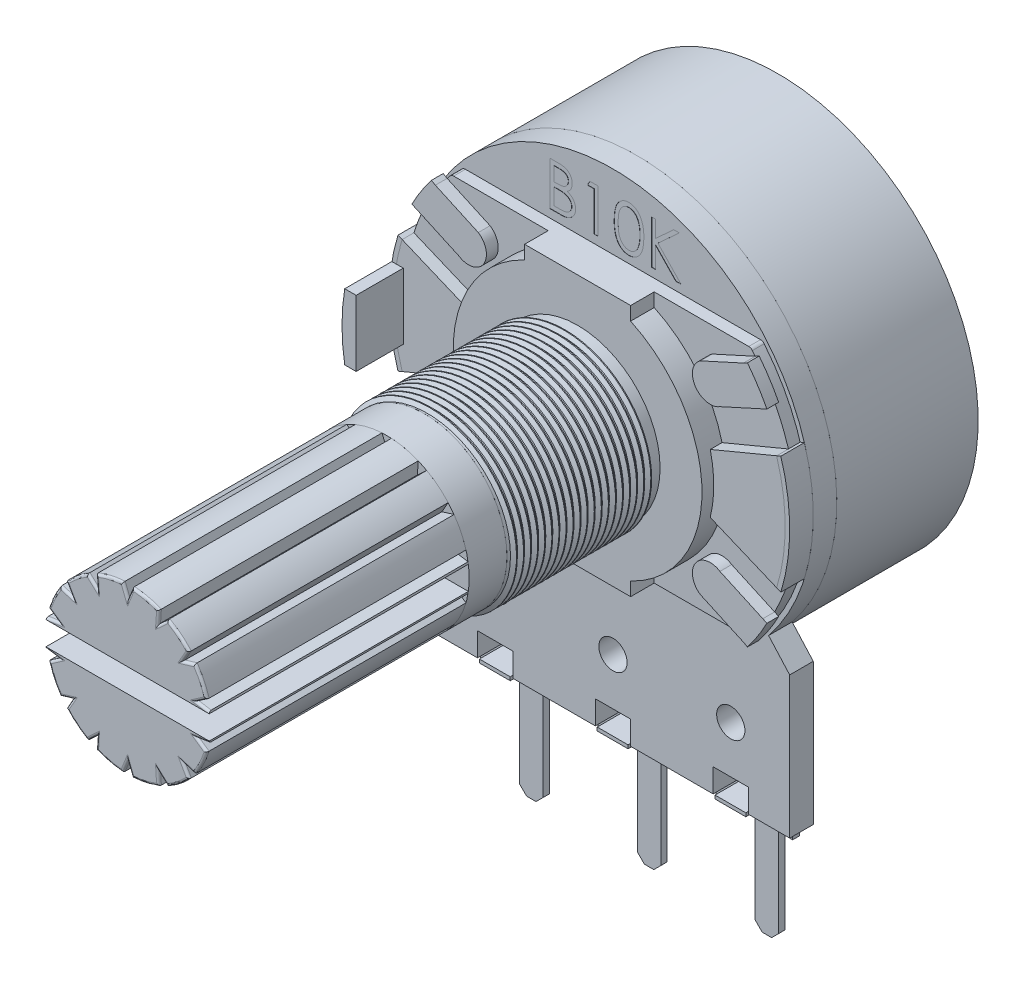
SolidWorks part; units mm, degrees
ref_plane "Alzado" through (0, 0, 0) normal (0, 0, 1) x (1, 0, 0)
ref_plane "Planta" through (0, 0, 0) normal (0, 1, 0) x (1, 0, 0)
ref_plane "Vista lateral" through (0, 0, 0) normal (1, 0, 0) x (0, 0, -1)
sketch "Croquis1" plane through (0, 0, 0) normal (0, 0, 1) x (1, 0, 0)
  circle A0 centre (0, 0) radius 8.5
  dimension "D1" = 17
extrude "Saliente-Extruir1" add sketch "Croquis1" along normal blind 6
sketch "Croquis2" plane through (0, 0, 0) normal (0, 0, -1) x (-1, 0, 0)
  line L0 (0, 0) -> (0, 8.5) construction
  line L1 (0, 0) -> (9.791, 0) construction
  line L2 (6.941, 1) -> (6.941, -1)
  line L3 (6.941, 1) -> (8.441, 1)
  line L4 (6.941, -1) -> (8.441, -1)
  circle A0 centre (0, 0) radius 8.5 construction
  arc A1 (8.441, 1) -> (8.441, -1) centre (0, 0) cw
  point P12 (6.941, 0)
  dimension "D1" = 1
  dimension "D2" = 1.5
extrude "Cortar-Extruir1" cut sketch "Croquis2" against normal blind 3 contours A1 L4 L2 L3
ref_plane "Plano1" through (0, -8.5, 0) normal (0, 1, 0) x (1, 0, 0)
sketch "Croquis3" plane through (0, -8.5, 0) normal (0, 1, 0) x (1, 0, 0)
  line L0 (0, 0) -> (0, -4.2789) construction
  line L1 (0, -4.2789) -> (0, -6) construction
  line L2 (-8.5, -6) -> (8.5, -6) construction
  line L3 (5.5, -3.5) -> (-5.5, -3.5)
  line L4 (-5.5, -3.5) -> (-5.5, -6)
  line L5 (-5.5, -6) -> (5.5, -6)
  line L6 (5.5, -3.5) -> (5.5, -6)
  point P11 (0, -3.5)
  dimension "D1" = 5.5
  dimension "D2" = 2.5
extrude "Cortar-Extruir2" cut sketch "Croquis3" along normal blind 5
sketch "Croquis4" plane through (0, 0, 6) normal (0, 0, 1) x (1, 0, 0)
  line L0 (-7.5, -12.3514) -> (7.5, -12.3514)
  line L1 (7.5, -12.3514) -> (7.5, -6.3514)
  line L2 (-7.5, -12.3514) -> (-7.5, -6.3514)
  line L3 (0, 0) -> (0, -14.8368) construction
  line L5 (6.604, -5.3514) -> (7.5, -6.3514)
  line L7 (-6.604, -5.3514) -> (-7.5, -6.3514)
  arc A0 (6.604, -5.3514) -> (-6.604, -5.3514) centre (0, 0) ccw
  arc A1 (5.5, -6.4807) -> (-5.5, -6.4807) centre (0, 0) ccw construction
  point P11 (0, -12.3514)
  dimension "D1" = 6
  dimension "D2" = 7.5
  dimension "D3" = 7
extrude "Saliente-Extruir2" add sketch "Croquis4" along normal blind 1 separate body
sketch "Croquis5" plane through (0, 0, 7) normal (0, 0, 1) x (1, 0, 0)
  line L0 (6.2625, -5.3514) -> (-6.2625, -5.3514)
  line L1 (0, 0) -> (4.67, 0) construction
  line L2 (6.2625, 5.3514) -> (-6.2625, 5.3514)
  line L3 (0, 8.5) -> (6.3562, 8.5) construction
  line L5 (0, 0) -> (0, 6.7087) construction
  line L6 (0, 0) -> (0, -6.9451) construction
  arc A1 (6.4169, 5.2784) -> (6.4169, -5.2784) centre (0, 0) cw
  arc A2 (6.4169, 5.2784) -> (6.2625, 5.3514) centre (6.2625, 5.1514) ccw
  arc A3 (6.2625, -5.3514) -> (6.4169, -5.2784) centre (6.2625, -5.1514) ccw
  arc A4 (-6.4169, 5.2784) -> (-6.2625, 5.3514) centre (-6.2625, 5.1514) cw
  arc A5 (-6.2625, -5.3514) -> (-6.4169, -5.2784) centre (-6.2625, -5.1514) cw
  arc A6 (-6.4169, 5.2784) -> (-6.4169, -5.2784) centre (0, 0) ccw
  point P9 (0, 5.3514)
  point P27 (0, -5.3514)
  dimension "D1" = 0.2
  dimension "D2" = 0.2
extrude "Saliente-Extruir3" add sketch "Croquis5" along normal blind 0.5 separate body
sketch "Croquis6" plane through (0, 0, 7.5) normal (0, 0, 1) x (1, 0, 0)
  line L0 (0, 0) -> (0, 6.118) construction
  line L1 (0, 0) -> (2.5948, 0) construction
  line L2 (8.124, -2.5) -> (5.1285, -1.25)
  line L6 (5.2787, 0) -> (8.5, 0)
  line L7 (8.124, 2.5) -> (5.1285, 1.25)
  line L8 (-8.124, -2.5) -> (-5.1285, -1.25)
  line L9 (-8.124, 2.5) -> (-5.1285, 1.25)
  arc A1 (6.604, -5.3514) -> (-6.604, -5.3514) centre (0, 0) ccw construction
  arc A3 (8.124, 2.5) -> (8.124, -2.5) centre (0, 0) cw
  arc A4 (-8.124, 2.5) -> (-8.124, -2.5) centre (0, 0) ccw
  arc A5 (5.1285, -1.25) -> (5.1285, 1.25) centre (0, 0) ccw
  arc A6 (-5.1285, -1.25) -> (-5.1285, 1.25) centre (0, 0) cw
  point P4 (5.1285, 0)
  arc M17 (6.4169, -5.2784) -> (6.4169, 5.2784) centre (0, 0) ccw
  arc M21 (-6.4169, 5.2784) -> (-6.4169, -5.2784) centre (0, 0) ccw
  dimension "D2" = 1.25
extrude "Saliente-Extruir4" add sketch "Croquis6" along normal blind 0.5 contours L9 L8 M21 | A5 L6 L7 M17 | A5 L2 L6 M17 region at (6.8677, -0.9571, 7.5) region at (6.8677, 0.9571, 7.5) region at (-6.8677, 0, 7.5)
sketch "Croquis7" plane through (0, 0, 7.5) normal (0, 0, 1) x (1, 0, 0)
  line L0 (0, 5.2787) -> (0, 5.8858) construction
  line L1 (-2.25, 5.3514) -> (2.25, 5.3514)
  line L2 (6.2625, 5.3514) -> (-6.2625, 5.3514) construction
  line L3 (2.25, 5.3514) -> (2.25, 4.7751)
  line L4 (0, 0) -> (0, 3.5555) construction
  line L5 (0, 0) -> (2.9172, 0) construction
  line L6 (-2.25, 5.3514) -> (-2.25, 4.7751)
  line L7 (-2.25, -5.3514) -> (2.25, -5.3514)
  line L8 (2.25, -5.3514) -> (2.25, -4.7751)
  line L9 (-2.25, -5.3514) -> (-2.25, -4.7751)
  arc A0 (-2.25, 4.7751) -> (-2.25, -4.7751) centre (0, 0) ccw
  arc A1 (2.25, -4.7751) -> (2.25, 4.7751) centre (0, 0) ccw
  point P13 (0, 5.3514)
  dimension "D1" = 2.25
extrude "Saliente-Extruir5" add sketch "Croquis7" along normal blind 1
sketch "Croquis8" plane through (0, 0, 7) normal (0, 0, 1) x (1, 0, 0)
  line L0 (0, -5.3514) -> (0, -10.1607) construction
  line L1 (-2.25, -5.3514) -> (2.25, -5.3514) construction
  line L2 (7.5, -9.3514) -> (-1.2858, -9.3514) construction
  line L3 (7.5, -12.3514) -> (7.5, -6.3514) construction
  circle A0 centre (0, -9.3514) radius 0.6
  circle A1 centre (5, -9.3514) radius 0.6
  circle A2 centre (-5, -9.3514) radius 0.6
  point P7 (0, 0)
  dimension "D1" = 1.2
  dimension "D2" = 2
  dimension "D3" = 2
extrude "Cortar-Extruir3" cut sketch "Croquis8" against normal blind 5
sketch "Croquis10" plane through (0, 0, 6) normal (0, 0, -1) x (-1, 0, 0)
  line L0 (0, -12.3514) -> (0, -6.0291) construction
  line L1 (7.5, -12.3514) -> (-7.5, -12.3514) construction
  line L2 (1.625, -9.3514) -> (1.625, -13.3514)
  line L3 (1.625, -13.3514) -> (1.125, -13.3514)
  line L4 (1.125, -13.3514) -> (0.8288, -13.2473)
  line L5 (-1.125, -13.3514) -> (-0.8288, -13.2473)
  line L6 (-1.625, -13.3514) -> (-1.125, -13.3514)
  line L7 (-1.625, -9.3514) -> (-1.625, -13.3514)
  line L8 (0, -9.3514) -> (0.815, -9.3514) construction
  line L21 (6.625, -9.3514) -> (6.625, -13.3514)
  line L22 (6.625, -13.3514) -> (6.125, -13.3514)
  line L23 (6.125, -13.3514) -> (5.8288, -13.2473)
  line L24 (3.875, -13.3514) -> (4.1712, -13.2473)
  line L25 (3.375, -13.3514) -> (3.875, -13.3514)
  line L26 (3.375, -9.3514) -> (3.375, -13.3514)
  line L27 (-3.375, -9.3514) -> (-3.375, -13.3514)
  line L28 (-3.375, -13.3514) -> (-3.875, -13.3514)
  line L29 (-3.875, -13.3514) -> (-4.1712, -13.2473)
  line L30 (-6.125, -13.3514) -> (-5.8288, -13.2473)
  line L31 (-6.625, -13.3514) -> (-6.125, -13.3514)
  line L32 (-6.625, -9.3514) -> (-6.625, -13.3514)
  arc A0 (-1.625, -9.3514) -> (1.625, -9.3514) centre (0, -9.3757) cw
  arc A1 (0.8288, -13.2473) -> (-0.8288, -13.2473) centre (0, -15.6059) ccw
  circle A9 centre (5, -9.3514) radius 0.6
  circle A10 centre (0, -9.3514) radius 0.6
  arc A11 (3.375, -9.3514) -> (6.625, -9.3514) centre (5, -9.3757) cw
  arc A12 (5.8288, -13.2473) -> (4.1712, -13.2473) centre (5, -15.6059) ccw
  arc A14 (-6.625, -9.3514) -> (-3.375, -9.3514) centre (-5, -9.3757) cw
  arc A15 (-4.1712, -13.2473) -> (-5.8288, -13.2473) centre (-5, -15.6059) ccw
  circle A16 centre (-5, -9.3514) radius 0.6
  point P17 (0, -12.9561)
  dimension "D4" = 2.5
  dimension "D1" = 2
  dimension "D2" = 0.5
  dimension "D3" = 1
  dimension "D5" = 2
  dimension "D6" = 2
extrude "Saliente-Extruir6" add sketch "Croquis10" along normal blind 0.3 separate body
sketch "Croquis11" plane through (0, 0, 0) normal (1, 0, 0) x (0, 0, -1)
  line L0 (-5.7, -12.9252) -> (-5.4, -12.9252)
  line L1 (-5.2, -13.1252) -> (-5.2, -17.9252)
  line L3 (-5.7, -12.9252) -> (-5.7, -13.1042)
  line L5 (-5.7, -13.1042) -> (-5.6655, -13.1042)
  line L6 (-5.4655, -13.3042) -> (-5.4655, -17.9252)
  line L7 (-5.4655, -17.9252) -> (-5.2, -17.9252)
  arc A0 (-5.6655, -13.1042) -> (-5.4655, -13.3042) centre (-5.6655, -13.3042) cw
  arc A1 (-5.2, -13.1252) -> (-5.4, -12.9252) centre (-5.4, -13.1252) ccw
  point P12 (-5.2, -12.9252)
  dimension "D3" = 0.2
  dimension "D1" = 5
  dimension "D2" = 0.5
extrude "Saliente-Extruir7" add sketch "Croquis11" along normal blind 0.5 and the other way blind 0.5
pattern_linear "MatrizL1" count 2 spacing 5 along (1, 0, 0) of "Saliente-Extruir7"
pattern_linear "MatrizL2" count 2 spacing 5 along (-1, 0, 0) of "Saliente-Extruir7"
chamfer "Chaflán1" distance 0.3 angle 45 2 edges at (4.5, -17.9252, 5.3328) (5.5, -17.9252, 5.3328)
chamfer "Chaflán2" distance 0.3 angle 45 2 edges at (-0.5, -17.9252, 5.3328) (0.5, -17.9252, 5.3328)
chamfer "Chaflán3" distance 0.3 angle 45 2 edges at (-4.5, -17.9252, 5.3328) (-5.5, -17.9252, 5.3328)
sketch "Croquis12" plane through (0, 0, 7) normal (0, 0, 1) x (1, 0, 0)
  line L0 (0, -12.3514) -> (0, -6.5599) construction
  line L1 (-7.5, -12.3514) -> (7.5, -12.3514) construction
  line L2 (-0.75, -11.3514) -> (0.75, -11.3514)
  line L3 (0.75, -11.3514) -> (0.75, -12.3514)
  line L4 (-0.75, -11.3514) -> (-0.75, -12.3514)
  line L5 (-0.75, -12.3514) -> (0.75, -12.3514)
  line L6 (4.25, -12.3514) -> (5.75, -12.3514)
  line L7 (5.75, -11.3514) -> (5.75, -12.3514)
  line L8 (4.25, -11.3514) -> (5.75, -11.3514)
  line L9 (4.25, -11.3514) -> (4.25, -12.3514)
  line L10 (-5.75, -12.3514) -> (-4.25, -12.3514)
  line L11 (-4.25, -11.3514) -> (-4.25, -12.3514)
  line L12 (-5.75, -11.3514) -> (-4.25, -11.3514)
  line L13 (-5.75, -11.3514) -> (-5.75, -12.3514)
  point P10 (0, -11.3514)
  dimension "D1" = 0.75
  dimension "D2" = 1
  dimension "D3" = 2
  dimension "D4" = 2
extrude "Cortar-Extruir4" cut sketch "Croquis12" against normal through all
sketch "Croquis13" plane through (0, 0, 6) normal (0, 0, 1) x (1, 0, 0)
  line L0 (4.25, -12.3514) -> (4.25, -11.3514)
  line L1 (4.25, -11.3514) -> (5.75, -11.3514)
  line L2 (5.75, -11.3514) -> (5.75, -12.3514)
  line L3 (5.75, -12.3514) -> (4.25, -12.3514)
  line L4 (0.75, -12.3514) -> (-0.75, -12.3514)
  line L5 (-0.75, -12.3514) -> (-0.75, -11.3514)
  line L6 (-0.75, -11.3514) -> (0.75, -11.3514)
  line L7 (0.75, -11.3514) -> (0.75, -12.3514)
  line L8 (-4.25, -12.3514) -> (-5.75, -12.3514)
  line L9 (-5.75, -12.3514) -> (-5.75, -11.3514)
  line L10 (-5.75, -11.3514) -> (-4.25, -11.3514)
  line L11 (-4.25, -11.3514) -> (-4.25, -12.3514)
  dimension "D1" = 3
extrude "Cortar-Extruir5" cut sketch "Croquis13" against normal blind 2
sketch "Croquis14" plane through (0, 0, 6) normal (0, 0, 1) x (1, 0, 0)
  line L0 (4.3314, -12.3514) -> (5.6395, -12.3514)
  line L1 (4.25, -12.3514) -> (5.75, -12.3514) construction
  line L2 (5.6395, -12.3514) -> (5.6395, -12.4982)
  line L3 (5.6395, -12.4982) -> (4.3314, -12.4982)
  line L4 (4.3314, -12.4982) -> (4.3314, -12.3514)
  line L5 (-0.6686, -12.4982) -> (-0.6686, -12.3514)
  line L6 (-0.6686, -12.3514) -> (0.6395, -12.3514)
  line L7 (0.6395, -12.3514) -> (0.6395, -12.4982)
  line L8 (0.6395, -12.4982) -> (-0.6686, -12.4982)
  line L9 (-5.6686, -12.4982) -> (-5.6686, -12.3514)
  line L10 (-5.6686, -12.3514) -> (-4.3605, -12.3514)
  line L11 (-4.3605, -12.3514) -> (-4.3605, -12.4982)
  line L12 (-4.3605, -12.4982) -> (-5.6686, -12.4982)
  dimension "D1" = 3
extrude "Saliente-Extruir8" add sketch "Croquis14" along normal blind 1
sketch "Croquis18" plane through (0, 0, 7.5) normal (0, 0, 1) x (1, 0, 0)
  line L0 (0, 0) -> (12.103, 0) construction
  line L1 (7.3598, -3.8564) -> (5.5397, -3.0275)
  line L2 (6.5371, -5.1289) -> (4.7169, -4.3)
  line L3 (7.3598, -3.8564) -> (7.5336, -3.9364)
  line L4 (6.5371, -5.1289) -> (6.7063, -5.2226)
  arc A0 (6.4169, -5.2784) -> (7.9469, -2.4261) centre (0, 0) ccw construction
  arc A1 (5.5397, -3.0275) -> (4.7169, -4.3) centre (5.1283, -3.6637) ccw
  arc A2 (6.604, -5.3514) -> (-6.604, -5.3514) centre (0, 0) ccw construction
  arc A3 (7.5336, -3.9364) -> (6.7063, -5.2226) centre (0, 0) cw
  dimension "D1" = 2
  dimension "D2" = 1.499
extrude "Saliente-Extruir9" add sketch "Croquis18" along normal blind 0.5
mirror "Simetría2" about plane through (0, 0, 0) normal (0, 1, 0) of "Saliente-Extruir9"
mirror "Simetría3" about plane through (0, 0, 0) normal (1, 0, 0) of "Simetría2"
sketch "Croquis19" plane through (0, 0, 8.5) normal (0, 0, 1) x (1, 0, 0)
  circle A0 centre (0, 0) radius 3.5
  dimension "D1" = 7
extrude "Saliente-Extruir10" add sketch "Croquis19" along normal blind 6.5
thread "Rosca1" pitch 0.3 method extrude profile "Perfil de rosca1" start angle 0, offset 0, length 6, pitch 0.3, diameter 7
ref_plane "Plano3" through (-3.5, 0, 15) normal (0, -1, 0) x (-1, 0, 0)
sketch "Perfil de rosca1" plane through (-3.5, 0, 15) normal (0, -1, 0) x (-1, 0, 0)
  line L0 (0, 0) -> (0, 0.3) construction
  line L1 (0, 0) -> (0.1624, 0.0937)
  line L2 (0.1624, 0.0937) -> (0.1624, 0.1312)
  line L3 (0.1624, 0.1312) -> (0, 0.225)
  line L4 (0.1624, 0.1125) -> (0, 0.1125) construction
  line L11 (0, 0) -> (0, 0.225)
  point P2 (0, 0)
  dimension "Pitch" = 0.3
  dimension "Profile_Angle" = 60
  dimension "Profile_Land" = 0.0375
  dimension "Profile_Height" = 0.1624
sketch "Croquis28" plane through (0, 0, 15) normal (0, 0, 1) x (1, 0, 0)
  circle A0 centre (0, 0) radius 3.5
extrude "Saliente-Extruir11" add sketch "Croquis28" along normal blind 1.6 separate body
sketch "Croquis29" plane through (0, 0, 16.6) normal (0, 0, 1) x (1, 0, 0)
  circle A0 centre (0, 0) radius 3.5
extrude "Saliente-Extruir12" add sketch "Croquis29" along normal blind 11 separate body
sketch "Croquis30" plane through (0, 0, 27.6) normal (0, 0, 1) x (1, 0, 0)
  line L0 (0, 0) -> (3.5, 0) construction
  line L1 (-3.4641, 0.5) -> (3.4641, 0.5)
  line L2 (-3.4641, -0.5) -> (3.4641, -0.5)
  arc A0 (-3.4641, 0.5) -> (-3.4641, -0.5) centre (0, 0) ccw
  arc A1 (3.4641, -0.5) -> (3.4641, 0.5) centre (0, 0) ccw
  point P6 (-3.4641, 0.5)
  point P7 (3.4641, 0.5)
  dimension "D1" = 0.5
extrude "Cortar-Extruir7" cut sketch "Croquis30" against normal blind 11 contours L1 A1 L2 A0
sketch "Croquis32" plane through (0, 0, 27.6) normal (0, 0, 1) x (1, 0, 0)
  line L0 (0, 0) -> (0, 3.5) construction
  line L1 (1.2992, 2.6978) -> (1.3359, 3.235)
  line L2 (0.2, 3.4943) -> (0, 2.9943)
  line L3 (0, 2.9943) -> (-0.2, 3.4943)
  line L4 (1.6963, 3.0615) -> (1.2992, 2.6978)
  line L5 (2.341, 1.8669) -> (2.6072, 2.335)
  line L6 (2.8566, 2.0223) -> (2.341, 1.8669)
  line L7 (2.9192, 0.6663) -> (3.3622, 0.9725)
  line L8 (3.4512, 0.5826) -> (2.9192, 0.6663)
  line L9 (2.9192, -0.6663) -> (3.4512, -0.5826)
  line L10 (3.3622, -0.9725) -> (2.9192, -0.6663)
  line L11 (2.341, -1.8669) -> (2.8566, -2.0223)
  line L12 (2.6072, -2.335) -> (2.341, -1.8669)
  line L13 (1.2992, -2.6978) -> (1.6963, -3.0615)
  line L14 (1.3359, -3.235) -> (1.2992, -2.6978)
  line L15 (0, -2.9943) -> (0.2, -3.4943)
  line L16 (-0.2, -3.4943) -> (0, -2.9943)
  line L17 (-1.2992, -2.6978) -> (-1.3359, -3.235)
  line L18 (-1.6963, -3.0615) -> (-1.2992, -2.6978)
  line L19 (-2.341, -1.8669) -> (-2.6072, -2.335)
  line L20 (-2.8566, -2.0223) -> (-2.341, -1.8669)
  line L21 (-2.9192, -0.6663) -> (-3.3622, -0.9725)
  line L22 (-3.4512, -0.5826) -> (-2.9192, -0.6663)
  line L23 (-2.9192, 0.6663) -> (-3.4512, 0.5826)
  line L24 (-3.3622, 0.9725) -> (-2.9192, 0.6663)
  line L25 (-2.341, 1.8669) -> (-2.8566, 2.0223)
  line L26 (-2.6072, 2.335) -> (-2.341, 1.8669)
  line L27 (-1.2992, 2.6978) -> (-1.6963, 3.0615)
  line L28 (-1.3359, 3.235) -> (-1.2992, 2.6978)
  arc A0 (0.2, 3.4943) -> (-0.2, 3.4943) centre (0, 0) ccw
  arc A1 (1.6963, 3.0615) -> (1.3359, 3.235) centre (0, 0) ccw
  arc A2 (2.8566, 2.0223) -> (2.6072, 2.335) centre (0, 0) ccw
  arc A3 (3.4512, 0.5826) -> (3.3622, 0.9725) centre (0, 0) ccw
  arc A4 (3.3622, -0.9725) -> (3.4512, -0.5826) centre (0, 0) ccw
  arc A5 (2.6072, -2.335) -> (2.8566, -2.0223) centre (0, 0) ccw
  arc A6 (1.3359, -3.235) -> (1.6963, -3.0615) centre (0, 0) ccw
  arc A7 (-0.2, -3.4943) -> (0.2, -3.4943) centre (0, 0) ccw
  arc A8 (-1.6963, -3.0615) -> (-1.3359, -3.235) centre (0, 0) ccw
  arc A9 (-2.8566, -2.0223) -> (-2.6072, -2.335) centre (0, 0) ccw
  arc A10 (-3.4512, -0.5826) -> (-3.3622, -0.9725) centre (0, 0) ccw
  arc A11 (-3.3622, 0.9725) -> (-3.4512, 0.5826) centre (0, 0) ccw
  arc A12 (-2.6072, 2.335) -> (-2.8566, 2.0223) centre (0, 0) ccw
  arc A13 (-1.3359, 3.235) -> (-1.6963, 3.0615) centre (0, 0) ccw
  point P48 (0, 0)
  dimension "D5" = 7
  dimension "D1" = 14
  dimension "D2" = 0.5
  dimension "D3" = 0.2
  dimension "D4" = 0.2
extrude "Cortar-Extruir8" cut sketch "Croquis32" against normal blind 11
fillet "Redondeo1" radius 0.1 20 edges at (0.7788, 3.4122, 27.6) (1.3175, 2.9664, 27.6) (1.4977, 2.8796, 27.6) (2.1822, 2.7364, 27.6) (2.4741, 2.101, 27.6) (2.5988, 1.9446, 27.6) (3.1534, 1.5186, 27.6) (3.1407, 0.8194, 27.6) (3.1852, 0.6244, 27.6) (-3.1852, 0.6244, 27.6) (-3.1407, 0.8194, 27.6) (-3.1534, 1.5186, 27.6) (-2.5988, 1.9446, 27.6) (-2.4741, 2.101, 27.6) (-2.1822, 2.7364, 27.6) (-1.4977, 2.8796, 27.6) (-1.3175, 2.9664, 27.6) (-0.7788, 3.4122, 27.6) (-0.1, 3.2443, 27.6) (0.1, 3.2443, 27.6)
fillet "Redondeo2" radius 0.1 20 edges at (3.1852, -0.6244, 27.6) (3.1407, -0.8194, 27.6) (3.1534, -1.5186, 27.6) (2.5988, -1.9446, 27.6) (2.4741, -2.101, 27.6) (2.1822, -2.7364, 27.6) (0.7788, -3.4122, 27.6) (1.4977, -2.8796, 27.6) (1.3175, -2.9664, 27.6) (0.1, -3.2443, 27.6) (-0.1, -3.2443, 27.6) (-0.7788, -3.4122, 27.6) (-1.3175, -2.9664, 27.6) (-1.4977, -2.8796, 27.6) (-2.1822, -2.7364, 27.6) (-2.4741, -2.101, 27.6) (-2.5988, -1.9446, 27.6) (-3.1852, -0.6244, 27.6) (-3.1407, -0.8194, 27.6) (-3.1534, -1.5186, 27.6)
sketch "Croquis33" plane through (0, 0, 7) normal (0, 0, 1) x (1, 0, 0)
  line L0 (-2.9162, 5.7003) -> (2.4725, 5.7003) construction
  text T0 "B10K" font "Century Gothic" height in points 7
  point P3 (-2.7426, 5.6924)
  point P4 (-2.9162, 5.7003)
extrude "Cortar-Extruir9" cut sketch "Croquis33" against normal blind 0.01
sketch "Croquis34" plane through (0, 0, 8) normal (0, 0, 1) x (1, 0, 0)
  line L0 (-7.9, 1.4) -> (-7.9, -1.4)
  line L1 (-8.5, 0) -> (-8.5, 4.0626) construction
  line L2 (-7.9, -1.4) -> (-8.3839, -1.4)
  line L3 (-7.9, 1.4) -> (-8.3839, 1.4)
  arc A0 (6.604, -5.3514) -> (-6.604, -5.3514) centre (0, 0) ccw construction
  arc A1 (-8.3839, 1.4) -> (-8.3839, -1.4) centre (0, 0) ccw
  point P7 (-7.9, 0)
  dimension "D1" = 1.2
  dimension "D2" = 2.8
extrude "Saliente-Extruir13" add sketch "Croquis34" along normal blind 2
sketch "Croquis9" plane through (0, 0, 7) normal (0, 0, 1) x (1, 0, 0)
  line L0 (7.9469, 2.4261) -> (8.1243, 2.4992)
  line L1 (0, 0) -> (9.2831, 0) construction
  line L2 (0, 0) -> (0, 4.4743) construction
  line L3 (7.9469, -2.4261) -> (8.1243, -2.4992)
  line L4 (-7.9469, -2.4261) -> (-8.1243, -2.4992)
  line L5 (-7.9469, 2.4261) -> (-8.1243, 2.4992)
  arc A0 (6.604, -5.3514) -> (-6.604, -5.3514) centre (0, 0) ccw construction
  arc A1 (-8.1243, 2.4992) -> (-8.1243, -2.4992) centre (0, 0) ccw
  arc A2 (7.9469, 2.4261) -> (7.9469, -2.4261) centre (0, 0) cw
  arc A3 (-7.9469, 2.4261) -> (-7.9469, -2.4261) centre (0, 0) ccw
  arc A4 (8.1243, 2.4992) -> (8.1243, -2.4992) centre (0, 0) cw
extrude "Saliente-Extruir14" add sketch "Croquis9" along normal blind 1 separate body
sketch "Croquis35" plane through (0, 0, 0) normal (0, 0, -1) x (-1, 0, 0)
  line L0 (-5.5885, 1.863) -> (6.9577, 1.863) construction
  line L1 (-3.6359, -2.3363) -> (5.4957, -2.3363) construction
  text T0 "ALPHA" font "Century Gothic" height in points 10
  text T1 "B10K" font "Century Gothic" height in points 10
  point P5 (5.4957, -2.2931)
  point P6 (-3.3553, -2.2715)
  point P7 (-3.6359, -2.3363)
extrude "Cortar-Extruir10" cut sketch "Croquis35" against normal blind 0.01
